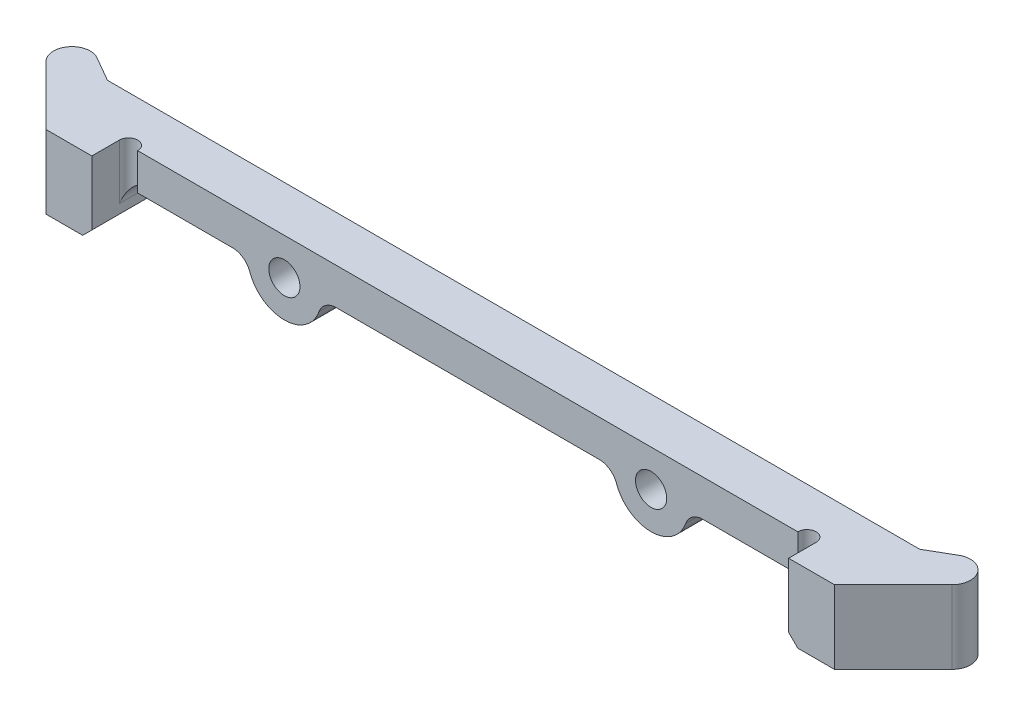
SolidWorks part; units mm, degrees
material "A2017"
ref_plane "正面" through (0, 0, 0) normal (0, 0, 1) x (1, 0, 0)
ref_plane "平面" through (0, 0, 0) normal (0, 1, 0) x (1, 0, 0)
ref_plane "右側面" through (0, 0, 0) normal (1, 0, 0) x (0, 0, -1)
sketch "ｽｹｯﾁ1" plane through (0, 0, 0) normal (0, 1, 0) x (1, 0, 0)
  line L0 (0, 0) -> (0, 22.3684) construction
  line L1 (-38, 0) -> (38, 0)
  line L2 (38, 0) -> (38, -3)
  line L3 (38, -3) -> (43, -3)
  line L4 (-38, -3) -> (-43, -3)
  line L5 (-38, 0) -> (-38, -3)
  line L6 (43, -3) -> (49.4142, 3.4142)
  line L7 (-43, -3) -> (-49.4142, 3.4142)
  line L8 (-44.2972, 5) -> (44.2972, 5)
  line L9 (47, 6.5605) -> (44.2972, 5)
  line L10 (50, 8.3293) -> (50, -3) construction
  line L11 (-50, 8.3293) -> (-50, -3) construction
  line L12 (-47, 6.5605) -> (-44.2972, 5)
  line L13 (-43, -3) -> (-49.4142, 3.4142)
  arc A0 (49.4142, 3.4142) -> (47, 6.5605) centre (48, 4.8284) ccw
  arc A1 (-49.4142, 3.4142) -> (-47, 6.5605) centre (-48, 4.8284) cw
  point P14 (0, 5)
  dimension "D8" = 2
  dimension "D1" = 5
  dimension "D2" = 3
  dimension "D3" = 76
  dimension "D4" = 45
  dimension "D5" = 30
  dimension "D6" = 5
  dimension "D7" = 100
extrude "ﾎﾞｽ - 押し出し1" add sketch "ｽｹｯﾁ1" along normal mid plane 8 contours A1 L7 L4 L5 L1 L2 L3 L6 A0 L9 L8 L12 region at (0, 0, -2.3316)
sketch "ｽｹｯﾁ2" plane through (0, 4, 0) normal (0, 1, 0) x (1, 0, 0)
  line L0 (-38, 0) -> (38, 0) construction
  circle A0 centre (-37, 0) radius 1
  circle A1 centre (37, 0) radius 1
  dimension "D1" = 2
extrude "ｶｯﾄ - 押し出し1" cut sketch "ｽｹｯﾁ2" against normal up to surface (8 mm away) up to face at (0, -4, -1.6722)
hole_wizard "M3 すきま穴1" positions "ｽｹｯﾁ3" profile "ｽｹｯﾁ4" hole size "M3" standard "JIS" end condition through all
sketch "ｽｹｯﾁ3" plane through (0, 0, 0) normal (0, 0, 1) x (1, 0, 0)
  point P0 (20, 0)
  point P3 (-20, 0)
sketch "ｽｹｯﾁ4" plane through (20, 0, 0) normal (1, 0, 0) x (0, -1, 0)
  line L0 (0, 0) -> (0, 6.8284)
  line L1 (0, 6.8284) -> (1.7, 6.8284)
  line L2 (1.7, 6.8284) -> (1.7, 0)
  line L5 (1.7, 0) -> (0, 0)
  line L11 (0, -6.35) -> (0, 107.95) construction
  dimension "通し穴の直径" = 3.4
  dimension "通し穴の深さ" = 6.8284
sketch "ｽｹｯﾁ5" plane through (0, 0, 0) normal (0, 0, 1) x (1, 0, 0)
  line L0 (-36, 4) -> (36, 4) construction
  line L2 (-38, -4) -> (38, -4)
  line L3 (-38, -4) -> (-38, 0)
  line L4 (-38, 0) -> (38, 0)
  line L5 (38, -4) -> (38, 0)
  line L6 (38, 4) -> (38, -4) construction
  circle A0 centre (-20, 0) radius 4
  circle A1 centre (20, 0) radius 4
  point P13 (38, 0)
  line M3 (-36, -4) -> (36, -4)
  line M4 (36, -4) -> (36, 4)
  line M6 (-36, 4) -> (-36, -4)
extrude "ｶｯﾄ - 押し出し2" cut sketch "ｽｹｯﾁ5" against normal through all contours A0 L4 M6 M3 | A1 L4 A0 L2 | A1 L4 M3 M4 | L2 L5 L4 M4 | L4 L3 L2 M6 region at (-37, -2, 0) region at (-29.5398, -2.0739, 0) region at (0, -2.0563, 0) region at (29.5398, -2.0739, 0) region at (37, -2, 0)
fillet "ﾌｨﾚｯﾄ1" radius 2 6 edges at (38, 0, -2.5) (24, 0, -2.5) (16, 0, -2.5) (-16, 0, -2.5) (-24, 0, -2.5) (-38, 0, -2.5)
chamfer "面取り1" distance 1 angle 45 2 edges at (-38, -4, -1) (38, -4, -1)
sketch "ｽｹｯﾁ6" plane through (0, 0, 0) normal (1, 0, 0) x (0, 0, -1)
  line L1 (5, 4) -> (13, 4)
  line L2 (5, 4) -> (5, -4)
  line L3 (5, -4) -> (13, -4)
  line L4 (13, 4) -> (13, -4)
  point P5 (5, -4)
  dimension "D1" = 8
extrude "ﾎﾞｽ - 押し出し2" [suppressed] add sketch "ｽｹｯﾁ6" along normal mid plane 10
fillet "ﾌｨﾚｯﾄ2" [suppressed] radius 3
sketch "ｽｹｯﾁ8" [suppressed] plane through (0, -4, 0) normal (0, -1, 0) x (1, 0, 0)
  line L0 (5, -5) -> (-5, -5) construction
  circle A0 centre (0, -5) radius 5
extrude "ﾎﾞｽ - 押し出し3" [suppressed] add sketch "ｽｹｯﾁ8" against normal up to surface (4 mm away) up to face at (0, 0, -2.5)
sketch "ｽｹｯﾁ7" [suppressed] plane through (0, -4, 0) normal (0, -1, 0) x (1, 0, 0)
  line L0 (0, -13) -> (0, -7) construction
  line L1 (5, -13) -> (-5, -13) construction
  line L2 (-3, -13) -> (-3, -7)
  line L3 (3, -13) -> (3, -7)
  arc A0 (-3, -13) -> (3, -13) centre (0, -13) ccw
  arc A1 (3, -7) -> (-3, -7) centre (0, -7) ccw
  point P5 (0, -10)
  point P10 (0, -8.8751)
  dimension "D1" = 6
  dimension "D2" = 6
extrude "ｶｯﾄ - 押し出し3" [suppressed] cut sketch "ｽｹｯﾁ7" against normal up to surface (8 mm away) up to face at (0, 4, -1.5762)
sketch "ｽｹｯﾁ9" [suppressed] plane through (0, -4, 0) normal (0, -1, 0) x (1, 0, 0)
  line L0 (-5, -5) -> (-5, -13) construction
  line L1 (-5, -7) -> (5, -7)
  line L2 (-5, -7) -> (-5, -11)
  line L3 (-5, -11) -> (5, -11)
  line L4 (5, -7) -> (5, -11)
  line L5 (5, -5) -> (5, -13) construction
  point P8 (5, -7.5525)
  dimension "D1" = 4
extrude "ｶｯﾄ - 押し出し4" [suppressed] cut sketch "ｽｹｯﾁ9" against normal blind 6
sketch "ｽｹｯﾁ10" [suppressed] plane through (0, 0, 0) normal (0, -1, 0) x (1, 0, 0)
  line L0 (-5, -8) -> (-5, -11) construction
  line L1 (-5, -7) -> (-5.1716, -7)
  line L2 (-5, -7) -> (-5, -8)
  line L3 (-5, -8) -> (-5.1716, -8)
  line L4 (-5.1716, -7) -> (-5.1716, -8)
  line L5 (0, 0) -> (0, -13.0364) construction
  line L6 (5.1716, -7) -> (5.1716, -8)
  line L7 (5, -8) -> (5.1716, -8)
  line L8 (5, -7) -> (5, -8)
  line L9 (5, -7) -> (5.1716, -7)
  arc A0 (-5, -8) -> (-8, -5) centre (-8, -8) ccw construction
extrude "ｶｯﾄ - 押し出し5" [suppressed] cut sketch "ｽｹｯﾁ10" against normal up to surface (2 mm away) up to face at (-43.8485, -4, -2.5055)
